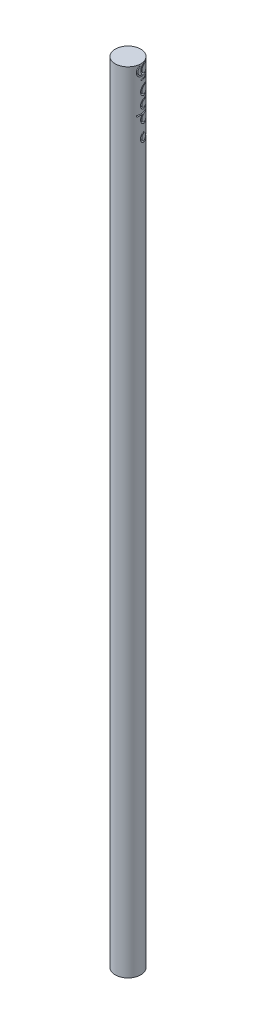
SolidWorks part; units mm, degrees
ref_plane "Front Plane" through (0, 0, 0) normal (0, 0, 1) x (1, 0, 0)
ref_plane "Top Plane" through (0, 0, 0) normal (0, 1, 0) x (1, 0, 0)
ref_plane "Right Plane" through (0, 0, 0) normal (1, 0, 0) x (0, 0, -1)
sketch "Sketch1" plane through (0, 0, 0) normal (0, 1, 0) x (1, 0, 0)
  circle A0 centre (0, 0) radius 1
  dimension "D1" = 2
extrude "Boss-Extrude1" add sketch "Sketch1" along normal blind 61.8
ref_plane "Plane1" through (1, 0, 0) normal (1, 0, 0) x (0, 0, -1)
sketch "Sketch2" plane through (1, 0, 0) normal (1, 0, 0) x (0, 0, -1)
  line L0 (0, 61.8) -> (0, 47.8345) construction
  line L1 (1, 61.8) -> (-1, 61.8) construction
  text T0 "group 3" font "Century Gothic" height in points 4
  point P5 (0, 50.3987)
  point P6 (0, 47.8345)
extrude "Cut-Extrude1" cut sketch "Sketch2" against normal blind 1
